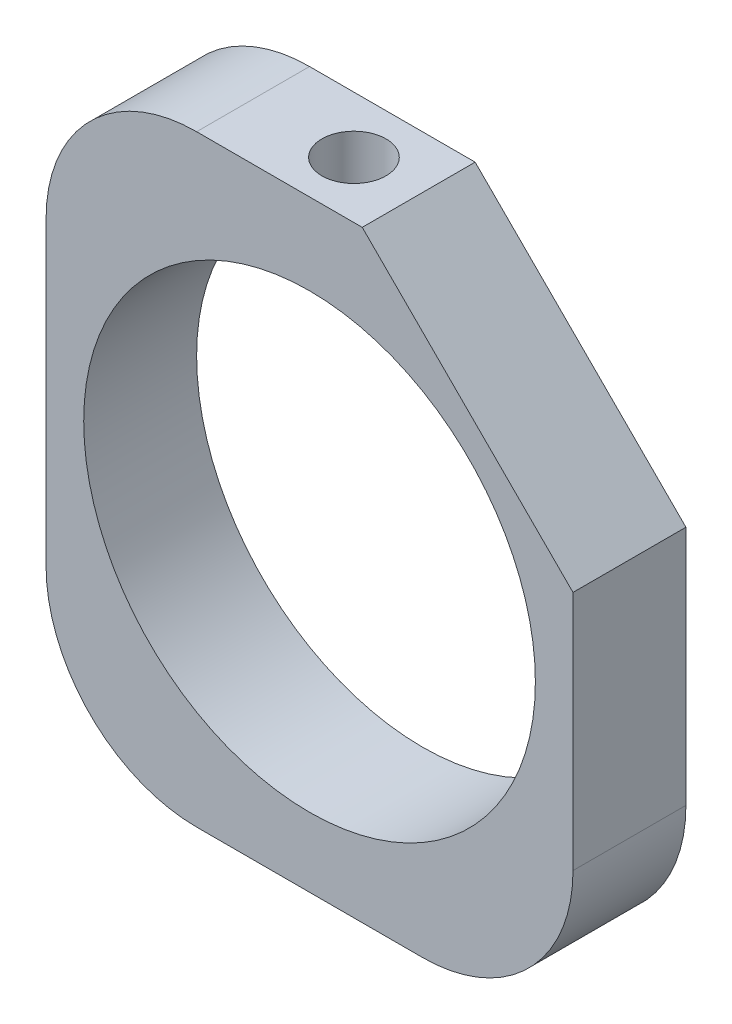
SolidWorks part; units mm, degrees
material "6063-O"
ref_plane "Front" through (0, 0, 0) normal (0, 0, 1) x (1, 0, 0)
ref_plane "Top" through (0, 0, 0) normal (0, 1, 0) x (1, 0, 0)
ref_plane "Right" through (0, 0, 0) normal (1, 0, 0) x (0, 0, -1)
sketch "Sketch1" plane through (0, 0, 0) normal (0, 0, 1) x (1, 0, 0)
  line L0 (11.1125, 12.446) -> (11.1125, 12.954)
  line L1 (4.7625, -12.446) -> (-4.7625, -12.446)
  line L2 (11.1125, -6.096) -> (11.1125, 12.446)
  line L3 (11.1125, 12.446) -> (-11.1125, 12.446)
  line L4 (-11.1125, -6.096) -> (-11.1125, 12.446)
  line L5 (11.1125, -12.446) -> (-11.1125, 12.446) construction
  line L6 (11.1125, 12.446) -> (-11.1125, -12.446) construction
  line L7 (11.1125, 12.954) -> (-4.7625, 12.954)
  line L8 (-11.1125, 6.604) -> (-11.1125, 12.446)
  circle A0 centre (0, 0) radius 9.525
  arc A1 (-11.1125, -6.096) -> (-4.7625, -12.446) centre (-4.7625, -6.096) ccw
  arc A2 (4.7625, -12.446) -> (11.1125, -6.096) centre (4.7625, -6.096) ccw
  arc A4 (-4.7625, 12.954) -> (-11.1125, 6.604) centre (-4.7625, 6.604) ccw
  point P0 (0, 0)
  point P18 (11.1125, 12.954)
  dimension "D3" = 19.05
  dimension "D5" = 6.35
  dimension "D1" = 22.225
  dimension "D2" = 24.892
  dimension "D4" = 0.508
extrude "Boss-Extrude2" add sketch "Sketch1" along normal blind 4.7625 contours L7 A4 L8 L3 L0 | L1 A2 L2 L3 L4 A1 A0 region at (2.3288, 12.6952, 0) region at (10.7788, 3.175, 0)
sketch "Sketch2" plane through (0, 12.954, 0) normal (0, 1, 0) x (1, 0, 0)
  line L0 (-11.1125, -2.3813) -> (-0.508, -2.3813)
  line L1 (-11.1125, -4.7625) -> (-11.1125, 0) construction
  line L3 (11.1125, -4.7625) -> (11.1125, 0) construction
  circle A0 centre (-0.508, -2.3813) radius 1.5875
  point P6 (11.1125, -2.3813)
  dimension "D2" = 3.175
  dimension "D1" = 10.6045
hole_wizard "Tap Drill for #6-32 Tap1" positions "Sketch5" profile "Sketch4" hole size "#6-32" standard "ANSI Inch"
sketch "Sketch5" plane through (0, 12.954, 0) normal (0, 1, 0) x (1, 0, 0)
  point P0 (-0.508, -2.3813)
sketch "Sketch4" plane through (-0.508, 12.954, 2.3813) normal (1, 0, 0) x (0, 0, 1)
  line L0 (0, 0) -> (0, 19.8627)
  line L1 (0, 19.8627) -> (1.3525, 19.05)
  line L2 (1.3525, 19.05) -> (1.3525, 0)
  line L5 (1.3525, 0) -> (0, 0)
  line L10 (0, 19.8627) -> (-1.3526, 19.05) construction
  line L11 (0, -6.35) -> (0, 107.95) construction
  dimension "Hole Dia." = 2.7051
  dimension "Hole Depth" = 19.05
  dimension "Drill Angle" = 118
chamfer "Chamfer1" distance 8.89 angle 45 1 edges at (11.1125, 12.954, 2.3813)
